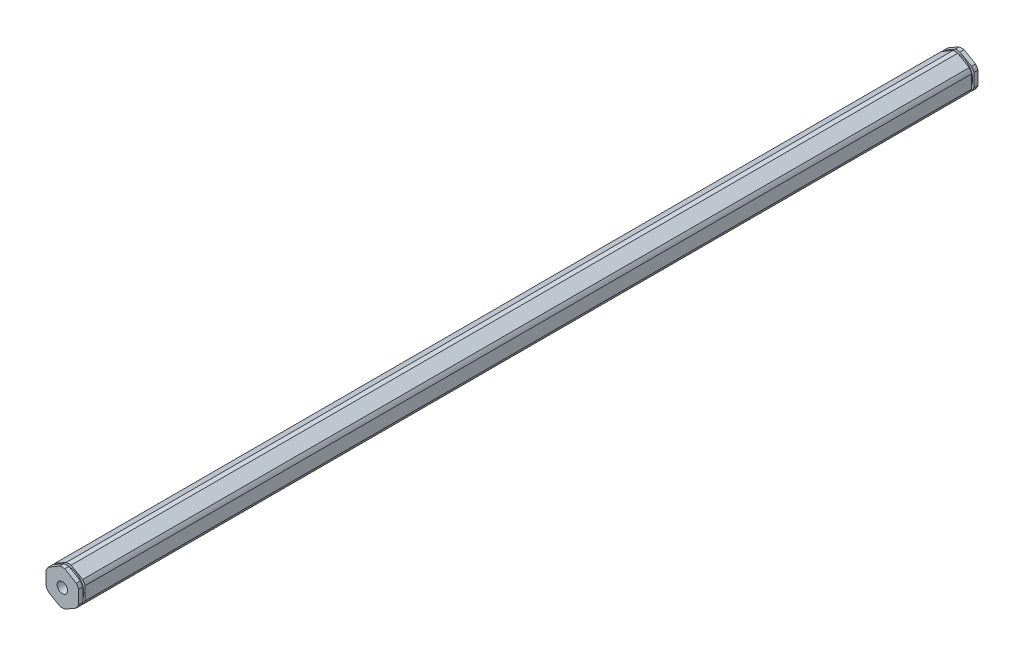
SolidWorks part; units mm, degrees
ref_plane "Front Plane" through (0, 0, 0) normal (0, 0, 1) x (1, 0, 0)
ref_plane "Top Plane" through (0, 0, 0) normal (0, 1, 0) x (1, 0, 0)
ref_plane "Right Plane" through (0, 0, 0) normal (1, 0, 0) x (0, 0, -1)
sketch "Sketch1" plane through (0, 0, 0) normal (0, 0, 1) x (1, 0, 0)
  line L1 (0, 7.3323) -> (-6.35, 3.6662)
  line L2 (-6.35, 3.6662) -> (-6.35, -3.6662)
  line L3 (-6.35, -3.6662) -> (0, -7.3323)
  line L4 (0, -7.3323) -> (6.35, -3.6662)
  line L5 (6.35, -3.6662) -> (6.35, 3.6662)
  line L6 (6.35, 3.6662) -> (0, 7.3323)
  circle A0 centre (0, 0) radius 6.35 construction
  circle A1 centre (0, 0) radius 6.858
  dimension "D1" = 12.7
  dimension "D2" = 13.716
extrude "Boss-Extrude1" add sketch "Sketch1" along normal mid plane 349.4405 contours L5 A1 L6 L1 L2 L3 L4 region at (0, 0, 0)
hole_wizard "#10-32 Tapped Hole1" positions "3DSketch1" profile "Sketch2" tap size "#10-32" standard "ANSI Inch"
sketch3d "3DSketch1"
  line L0 (0, 0, 174.7202) -> (0, 0, -174.7202) construction
  line L1 (0, 0, 174.7202) -> (0, 0, -174.7202) construction
  point P0 (0, 0, 174.7202)
  point P4 (0, 0, -174.7202)
sketch "Sketch2" plane through (0, 0, 174.7202) normal (1, 0, 0) x (0, -1, 0)
  line L0 (0, 0) -> (0, 17.5608)
  line L1 (0, 17.5608) -> (2.0193, 16.3474)
  line L2 (2.0193, 16.3474) -> (2.0193, 0)
  line L5 (2.0193, 0) -> (0, 0)
  line L10 (0, 17.5608) -> (-2.0193, 16.3474) construction
  line L11 (0, -6.35) -> (0, 107.95) construction
  dimension "Tap Drill Dia." = 4.0386
  dimension "Tap Drill Depth" = 16.3474
  dimension "Drill Angle" = 118
cosmetic thread "Hole Thread1" parameters "D1"=13.97, "D2"=4.826
cosmetic thread "Hole Thread2" parameters "D1"=13.97, "D2"=4.826
sketch "Sketch3" plane through (0, 0, 0) normal (1, 0, 0) x (0, 0, -1)
  line L0 (-175.1574, 0) -> (-171.1173, 0) construction
  line L1 (174.7202, 6.858) -> (-174.7202, 6.858) construction
  line L2 (-173.1327, 6.858) -> (-172.2438, 6.858)
  line L3 (-173.1327, 6.858) -> (-173.1328, 5.8547)
  line L4 (-173.1328, 5.8547) -> (-172.2438, 5.8547)
  line L5 (-172.2438, 6.858) -> (-172.2438, 5.8547)
  dimension "D1" = 0.889
  dimension "D2" = 5.8547
  dimension "D3" = 1.5875
revolve "Cut-Revolve1" cut sketch "Sketch3" angle 360 about L0
mirror "Mirror1" about plane through (0, 0, 0) normal (0, 0, 1) of "Cut-Revolve1"
